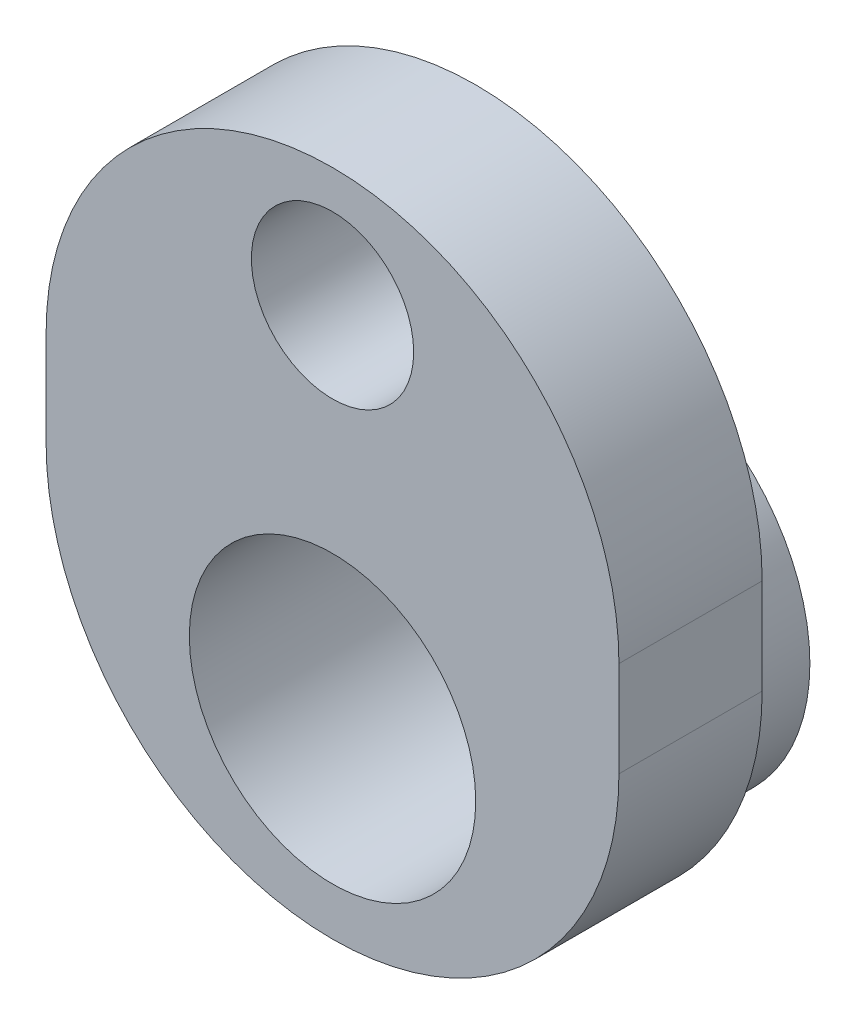
SolidWorks part; units mm, degrees
ref_plane "Płaszczyzna przednia" through (0, 0, 0) normal (0, 0, 1) x (1, 0, 0)
ref_plane "Płaszczyzna górna" through (0, 0, 0) normal (0, 1, 0) x (1, 0, 0)
ref_plane "Płaszczyzna prawa" through (0, 0, 0) normal (1, 0, 0) x (0, 0, -1)
sketch "Sketch1" plane through (0, 0, 0) normal (0, 0, 1) x (1, 0, 0)
  line L0 (-6, 4) -> (-6, 2)
  line L1 (6, 4) -> (6, 2)
  circle A0 centre (0, 0) radius 3
  circle A1 centre (0, 7.5) radius 1.7
  circle A2 centre (0, 0) radius 4
  circle A3 centre (0, 2) radius 6
  circle A4 centre (0, 4) radius 6
  dimension "D1" = 6
  dimension "D2" = 3.4
  dimension "D5" = 12
  dimension "D6" = 12
  dimension "D3" = 7.5
  dimension "D7" = 2
  dimension "D4" = 1
extrude "Boss-Extrude1" add sketch "Sketch1" along normal blind 3 contours A4 A3 A1 | A4 L0 A3 | A3 A4 A2 A1 | A4 A3 A2 | A2 A4 A0 | A4 A2 A3 | A4 A2 A0 | A4 A3 L1 region at (-5.9749, 3, 0) region at (0, 9.8611, 0) region at (-4.4934, -0.8064, 0) region at (5.9749, 3, 0) region at (0, 4.2043, 0) region at (-2.5884, -2.9349, 0) region at (4.4934, -0.8064, 0) region at (-0.2445, 3.896, 0)
extrude "Boss-Extrude2" add sketch "Sketch1<3>" against normal blind 3 contours A2 A4 A0 | A4 A2 A0 region at (-2.5884, -2.9349, 0) region at (-0.2445, 3.896, 0)
sketch "Sketch1<3>" plane through (0, 0, 0) normal (0, 0, 1) x (1, 0, 0) same geometry as "Sketch1"
